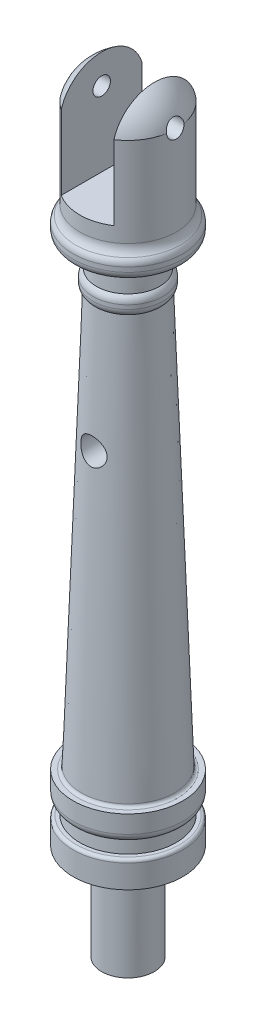
SolidWorks part; units mm, degrees
ref_plane "Front Plane" through (0, 0, 0) normal (0, 0, 1) x (1, 0, 0)
ref_plane "Top Plane" through (0, 0, 0) normal (0, 1, 0) x (1, 0, 0)
ref_plane "Right Plane" through (0, 0, 0) normal (1, 0, 0) x (0, 0, -1)
sketch "Sketch1" plane through (0, 0, 0) normal (0, 0, 1) x (1, 0, 0)
  line L0 (0, 0) -> (0, 114)
  line L1 (0, 0) -> (11, 0)
  line L2 (0, 114) -> (7, 114)
  line L3 (11, 0) -> (7, 114)
revolve "Revolve1" add sketch "Sketch1" angle 360 about L0
sketch "Sketch2" plane through (0, 0, 0) normal (0, -1, 0) x (1, 0, 0)
  circle A0 centre (0, 0) radius 12.5
extrude "Boss-Extrude1" add sketch "Sketch2" along normal blind 6
sketch "Sketch3" plane through (0, -6, 0) normal (0, -1, 0) x (1, 0, 0)
  circle A1 centre (0, 0) radius 12.5
  circle A2 centre (0, 0) radius 12.5
  dimension "D1" = 0
extrude "Boss-Extrude2" add sketch "Sketch3" along normal mid plane 6 from offset 12 offset against normal yes
fillet "Fillet1" radius 2 1 edges at (0, 3, -12.5)
fillet "Fillet2" radius 0.7 1 edges at (0, 0, -12.5)
sketch "Sketch4" plane through (0, -6, 0) normal (0, -1, 0) x (1, 0, 0)
  circle A0 centre (0, 0) radius 6
extrude "Boss-Extrude3" add sketch "Sketch4" along normal blind 22
sketch "Sketch5" plane through (0, -28, 0) normal (0, -1, 0) x (-1, 0, 0)
  line L0 (5, -3.3166) -> (5, 3.3166)
  circle A0 centre (0, 0) radius 6 construction
  circle A1 centre (0, 0) radius 6 construction
  circle A3 centre (0, 0) radius 6
  arc A4 (5, -3.3166) -> (5, 3.3166) centre (0, 0) ccw
  point P6 (5, 0)
  dimension "D1" = 5
  dimension "D2" = 0
extrude "Cut-Extrude1" cut sketch "Sketch5" against normal blind 15
sketch "Sketch6" plane through (0, 114, 0) normal (0, 1, 0) x (1, 0, 0)
  circle A0 centre (0, 0) radius 8
extrude "Boss-Extrude4" add sketch "Sketch6" along normal mid plane 4 from offset 8 offset against normal yes
fillet "Fillet3" radius 2 2 edges at (0, 104, 8) (0, 108, 8)
sketch "Sketch7" plane through (0, 114, 0) normal (0, 1, 0) x (1, 0, 0)
  circle A0 centre (0, 0) radius 12.5
extrude "Boss-Extrude5" add sketch "Sketch7" along normal blind 5
sketch "Sketch8" plane through (0, 119, 0) normal (0, 1, 0) x (1, 0, 0)
  circle A0 centre (0, 0) radius 11
extrude "Boss-Extrude6" add sketch "Sketch8" along normal blind 22
fillet "Fillet4" radius 2 2 edges at (0, 114, 12.5) (0, 119, 12.5)
fillet "Fillet5" radius 3 1 edges at (0, 119, 11)
fillet "Fillet6" radius 0.7 1 edges at (0, 9, -10.6842)
sketch "Sketch9" plane through (0, 0, 0) normal (0, 0, 1) x (1, 0, 0)
  line L0 (11, 141) -> (0, 141)
  line L1 (11, 141) -> (-11, 141) construction
  line L2 (0, 141) -> (0, 149.2836)
  arc A0 (0, 149.2836) -> (11, 141) centre (0.3393, 138.2889) cw
revolve "Revolve2" add sketch "Sketch9" angle 360 about L2
sketch "Sketch10" plane through (0, 0, 0) normal (0, 0, 1) x (1, 0, 0)
  line L0 (0, 120.1553) -> (0, 151.6553) construction
  line L1 (11, 141) -> (-11, 141) construction
  line L2 (-6, 152) -> (6, 152)
  line L3 (-6, 152) -> (-6, 124)
  line L4 (-6, 124) -> (6, 124)
  line L5 (6, 152) -> (6, 124)
  dimension "D1" = 12
  dimension "D2" = 17
extrude "Cut-Extrude2" cut sketch "Sketch10" against normal through all both and the other way through all
sketch "Sketch11" plane through (0, 0, 0) normal (0, 0, 1) x (1, 0, 0)
  line L1 (-6, -6) -> (6, -6) construction
  circle A0 centre (0, 76) radius 3
  dimension "D2" = 6
  dimension "D1" = 82
extrude "Cut-Extrude3" cut sketch "Sketch11" against normal through all both and the other way through all
sketch "Sketch12" plane through (0, 0, 0) normal (1, 0, 0) x (0, 0, -1)
  line L0 (-9.2195, 141) -> (9.2195, 141) construction
  circle A0 centre (0, 141) radius 2
extrude "Cut-Extrude4" cut sketch "Sketch12" against normal through all both and the other way through all
